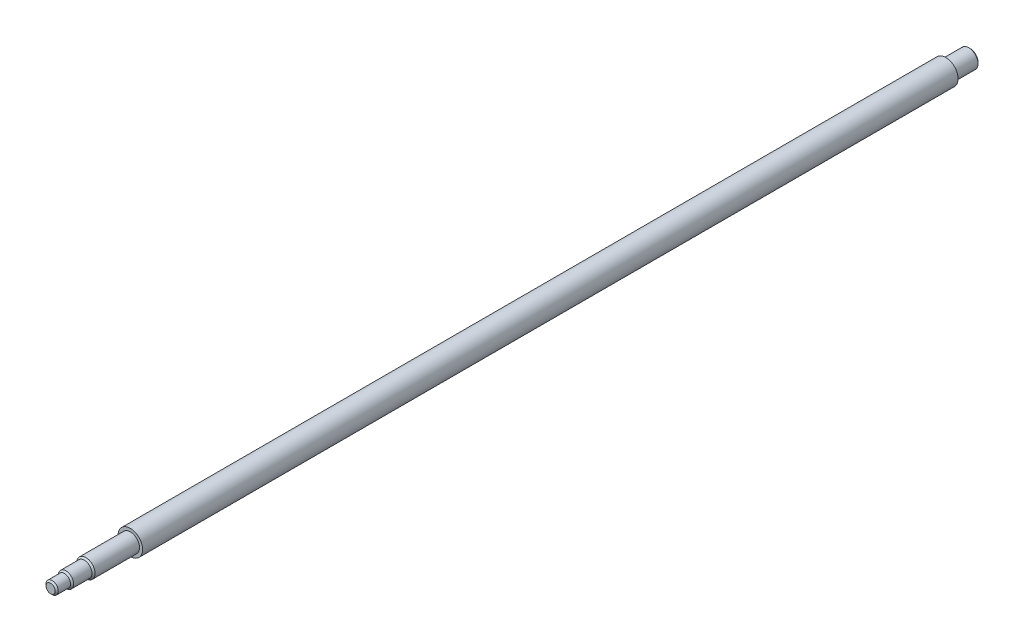
SolidWorks part; units mm, degrees
material "1.0037 (S235JR)"
ref_plane "Płaszczyzna przednia" through (0, 0, 0) normal (0, 0, 1) x (1, 0, 0)
ref_plane "Płaszczyzna górna" through (0, 0, 0) normal (0, 1, 0) x (1, 0, 0)
ref_plane "Płaszczyzna prawa" through (0, 0, 0) normal (1, 0, 0) x (0, 0, -1)
sketch "Szkic1" plane through (0, 0, 0) normal (1, 0, 0) x (0, 0, -1)
  line L0 (0, 0) -> (600, 0)
  line L1 (600, 0) -> (600, 6)
  line L2 (600, 6) -> (584, 6)
  line L3 (584, 6) -> (584, 8)
  line L4 (584, 8) -> (52, 8)
  line L5 (52, 8) -> (52, 6)
  line L6 (52, 6) -> (22, 6)
  line L7 (22, 6) -> (22, 5)
  line L8 (22, 5) -> (9, 5)
  line L9 (0, 4) -> (0, 0)
  line L10 (0, 4) -> (9, 4)
  line L11 (9, 4) -> (9, 5)
  dimension "D1" = 600
  dimension "D2" = 6
  dimension "D3" = 5
  dimension "D4" = 6
  dimension "D5" = 8
  dimension "D6" = 16
  dimension "D7" = 30
  dimension "D8" = 13
  dimension "D9" = 9
  dimension "D10" = 4
revolve "Obrót1" add sketch "Szkic1" angle 360 about L0
chamfer "Sfazowanie1" distance 1 angle 45 3 edges at (4, 0, 0) (5, 0, -9) (6, 0, -22)
chamfer "Sfazowanie2" distance 1 angle 45 1 edges at (6, 0, -600)
